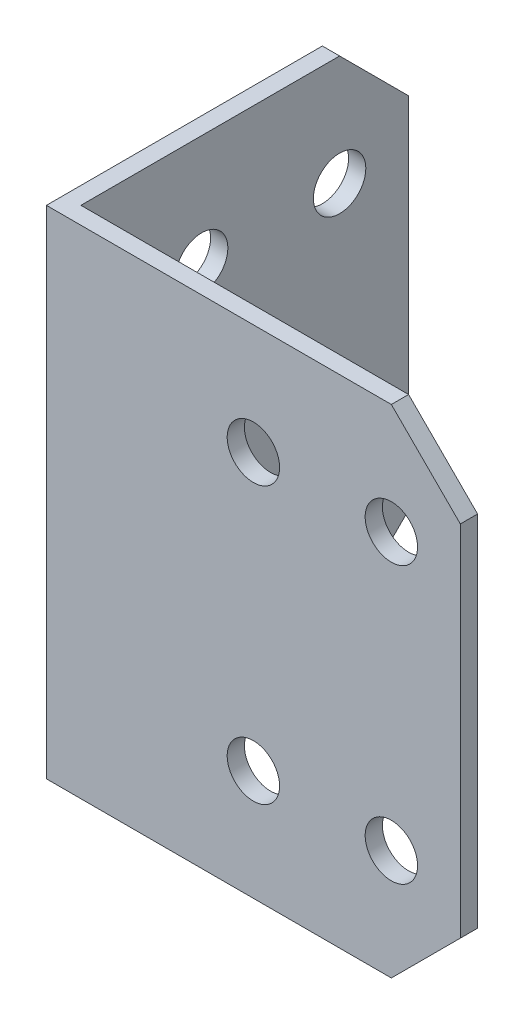
SolidWorks part; units mm, degrees
material "6061-T6 (SS)"
ref_plane "Front Plane" through (0, 0, 0) normal (0, 0, 1) x (1, 0, 0)
ref_plane "Top Plane" through (0, 0, 0) normal (0, 1, 0) x (1, 0, 0)
ref_plane "Right Plane" through (0, 0, 0) normal (1, 0, 0) x (0, 0, -1)
sketch "Sketch1" plane through (0, 0, 0) normal (0, 1, 0) x (1, 0, 0)
  line L1 (-18.1093, 25.3412) -> (-16.5218, 25.3412)
  line L2 (-18.1093, 25.3412) -> (-18.1093, -6.4088)
  line L4 (-16.5218, 25.3412) -> (-16.5218, -4.8213)
  line L5 (-18.1093, -6.4088) -> (19.9907, -6.4088)
  line L7 (-16.5218, -4.8213) -> (19.9907, -4.8213)
  line L8 (19.9907, -6.4088) -> (19.9907, -4.8213)
  dimension "D1" = 1.5875
  dimension "D2" = 1.5875
  dimension "D3" = 31.75
  dimension "D4" = 38.1
extrude "Boss-Extrude1" add sketch "Sketch1" along normal blind 45.72 contours L2 L5 L8 L7 L4 L1
sketch "Sketch2" plane through (0, 0, 4.8213) normal (0, 0, -1) x (-1, 0, 0)
  line L1 (-13.6407, 35.56) -> (-0.9407, 35.56) construction
  line L2 (-13.6407, 35.56) -> (-13.6407, 10.16) construction
  line L3 (-13.6407, 10.16) -> (-0.9407, 10.16) construction
  line L4 (-0.9407, 35.56) -> (-0.9407, 10.16) construction
  line L5 (18.1093, 45.72) -> (18.1093, 0) construction
  line L6 (16.5218, 45.72) -> (-19.9907, 45.72) construction
  circle A0 centre (-0.9407, 35.56) radius 2.413
  circle A1 centre (-13.6407, 35.56) radius 2.413
  circle A2 centre (-13.6407, 10.16) radius 2.413
  circle A3 centre (-0.9407, 10.16) radius 2.413
  dimension "D5" = 4.826
  dimension "D1" = 12.7
  dimension "D2" = 19.05
  dimension "D3" = 10.16
  dimension "D4" = 25.4
extrude "Cut-Extrude1" cut sketch "Sketch2" against normal through all
sketch "Sketch3" plane through (-16.5218, 0, 0) normal (1, 0, 0) x (0, 0, -1)
  line L0 (-6.4088, 45.72) -> (-6.4088, 0) construction
  line L1 (18.9912, 35.56) -> (6.2912, 35.56) construction
  line L2 (18.9912, 35.56) -> (18.9912, 10.16) construction
  line L3 (18.9912, 10.16) -> (6.2912, 10.16) construction
  line L4 (6.2912, 35.56) -> (6.2912, 10.16) construction
  line L5 (25.3412, 45.72) -> (-4.8213, 45.72) construction
  circle A0 centre (6.2912, 35.56) radius 2.413
  circle A1 centre (18.9912, 35.56) radius 2.413
  circle A2 centre (18.9912, 10.16) radius 2.413
  circle A3 centre (6.2912, 10.16) radius 2.413
  dimension "D5" = 4.826
  dimension "D1" = 12.7
  dimension "D2" = 25.4
  dimension "D3" = 10.16
  dimension "D4" = 12.7
extrude "Cut-Extrude2" cut sketch "Sketch3" against normal through all
chamfer "Chamfer1" distance 6.35 angle 45 4 edges at (19.9907, 45.72, 5.615) (19.9907, 0, 5.615) (-17.3155, 0, -25.3412) (-17.3155, 45.72, -25.3412)
